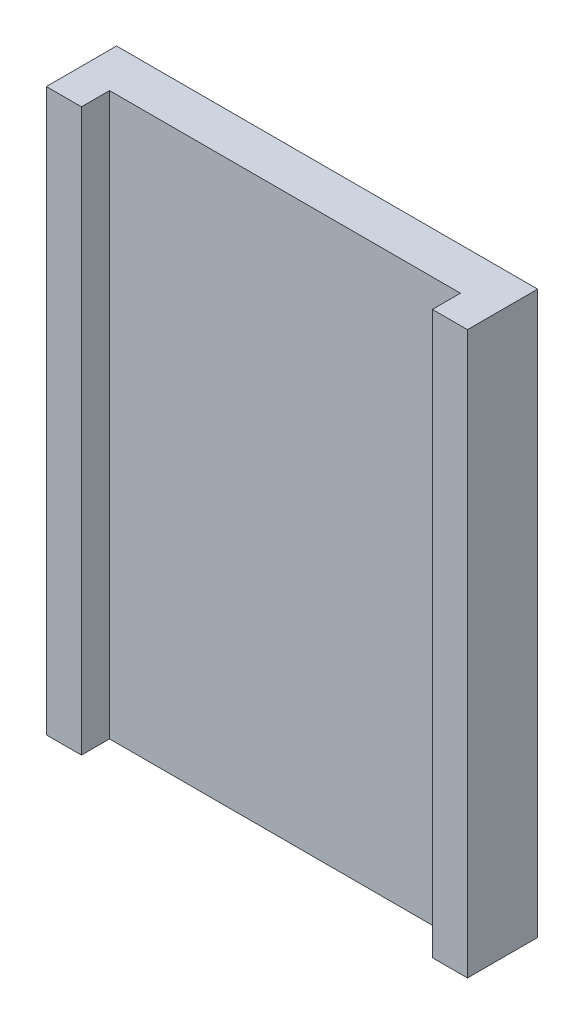
SolidWorks part; units mm, degrees
ref_plane "Front Plane" through (0, 0, 0) normal (0, 0, 1) x (1, 0, 0)
ref_plane "Top Plane" through (0, 0, 0) normal (0, 1, 0) x (1, 0, 0)
ref_plane "Right Plane" through (0, 0, 0) normal (1, 0, 0) x (0, 0, -1)
sketch "Sketch1" plane through (0, 0, 0) normal (0, 0, 1) x (1, 0, 0)
  line L1 (-3.75, 5) -> (3.75, 5)
  line L2 (-3.75, 5) -> (-3.75, -5)
  line L3 (-3.75, -5) -> (3.75, -5)
  line L4 (3.75, 5) -> (3.75, -5)
  line L5 (-3.75, 5) -> (3.75, -5) construction
  line L6 (-3.75, -5) -> (3.75, 5) construction
  line L7 (-3.125, 5) -> (3.125, 5)
  line L8 (-3.125, 5) -> (-3.125, -5)
  line L9 (-3.125, -5) -> (3.125, -5)
  line L10 (3.125, 5) -> (3.125, -5)
  line L11 (-3.125, 5) -> (3.125, -5) construction
  line L12 (-3.125, -5) -> (3.125, 5) construction
  point P0 (0, 0)
  point P6 (0, 0)
  dimension "D1" = 7.5
  dimension "D2" = 10
  dimension "D3" = 10
  dimension "D4" = 6.25
extrude "Boss-Extrude1" add sketch "Sketch1" along normal blind 0.75 contours L10 L1 L8 L3 region at (0, 0, 0)
extrude "Boss-Extrude2" add sketch "Sketch1<3>" along normal blind 1.25 contours L1 L10 L3 L4 | L8 L1 L2 L3 region at (-3.4375, 0, 0) region at (3.4375, 0, 0)
sketch "Sketch1<3>" plane through (0, 0, 0) normal (0, 0, 1) x (1, 0, 0) same geometry as "Sketch1"
equation "\"D3@Sketch1\"=\"D2@Sketch1\""
